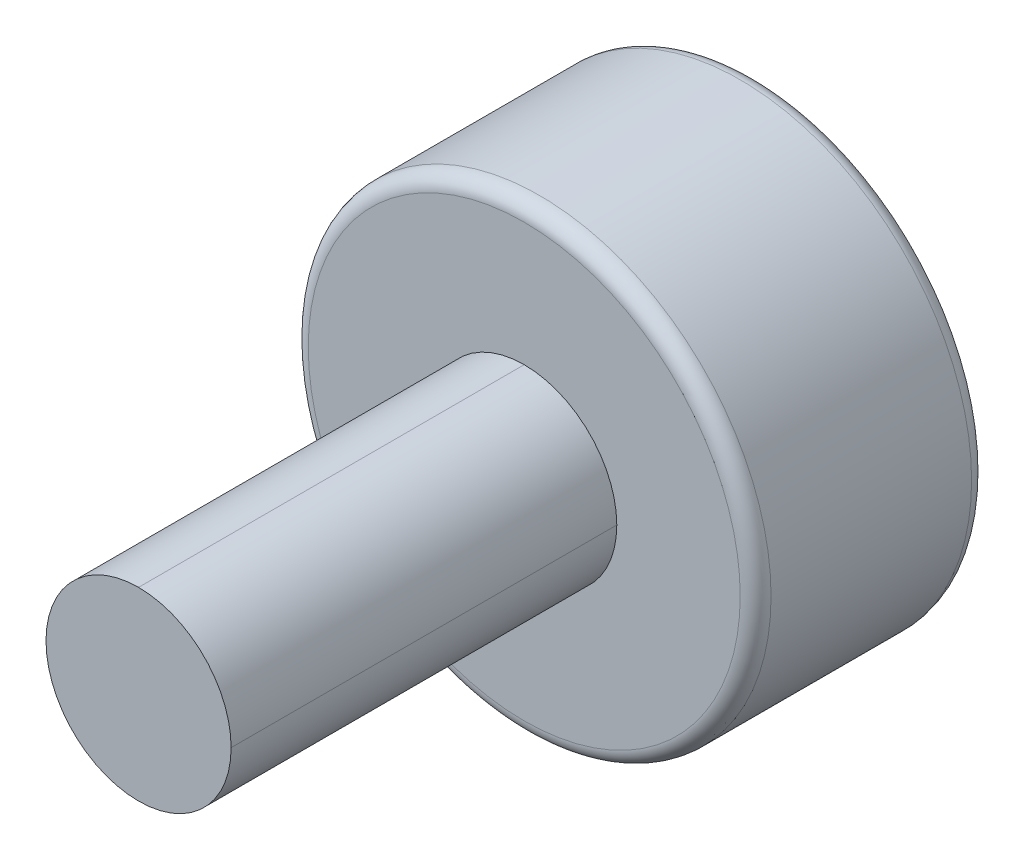
SolidWorks part; units mm, degrees
ref_plane "Plan de face" through (0, 0, 0) normal (0, 0, 1) x (1, 0, 0)
ref_plane "Plan de dessus" through (0, 0, 0) normal (0, 1, 0) x (1, 0, 0)
ref_plane "Plan de droite" through (0, 0, 0) normal (1, 0, 0) x (0, 0, -1)
sketch "Esquisse1" plane through (0, 0, 0) normal (0, 0, 1) x (1, 0, 0)
  line L0 (12, 12) -> (-12, -12) construction
  line L1 (-12, 12) -> (12, 12)
  line L2 (-12, 12) -> (-12, -12)
  line L3 (-12, -12) -> (12, -12)
  line L4 (12, 12) -> (12, -12)
  line L5 (-12, 12) -> (12, -12) construction
  point P4 (0, 0)
  dimension "D1" = 24
  dimension "D2" = 24
extrude "Boss.-Extru.1" add sketch "Esquisse1" along normal blind 50
sketch "Esquisse2" plane through (0, 0, 0) normal (0, 0, 1) x (1, 0, 0)
  circle A0 centre (0, 0) radius 2.5
  dimension "D1" = 5
extrude "Boss.-Extru.3" add sketch "Esquisse2" against normal blind 30
sketch "Esquisse3" plane through (0, 0, 0) normal (0, 0, 1) x (1, 0, 0)
  circle A0 centre (0, 0) radius 30
  circle A1 centre (0, 0) radius 2.5
  dimension "D1" = 60
  dimension "D2" = 5
extrude "Boss.-Extru.4" add sketch "Esquisse3" against normal blind 30 contours A0
fillet "Congé1" radius 2 1 edges at (30, 0, -30)
fillet "Congé2" radius 2 1 edges at (30, 0, 0)
fillet "Congé3" radius 12 4 edges at (-12, 12, 25) (12, 12, 25) (12, -12, 25) (-12, -12, 25)
